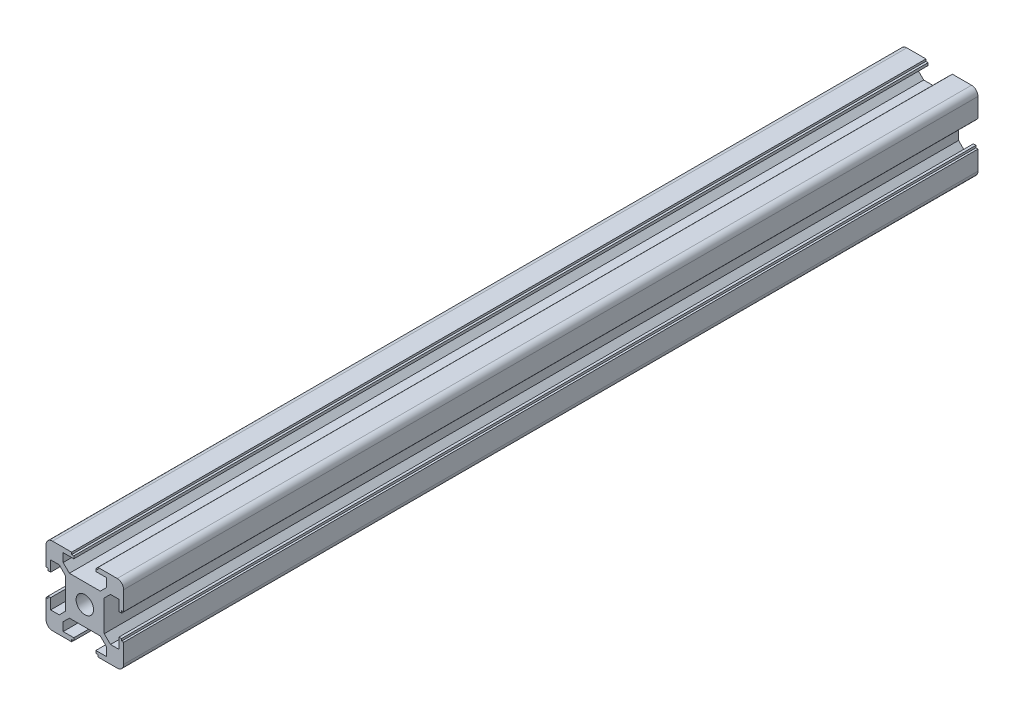
SolidWorks part; units mm, degrees
ref_plane "Front Plane" through (0, 0, 0) normal (0, 0, 1) x (1, 0, 0)
ref_plane "Top Plane" through (0, 0, 0) normal (0, 1, 0) x (1, 0, 0)
ref_plane "Right Plane" through (0, 0, 0) normal (1, 0, 0) x (0, 0, -1)
sketch "Sketch1" plane through (0, 0, 0) normal (0, 0, 1) x (1, 0, 0)
  line L1 (-15, -15) -> (15, -15)
  line L2 (-15, -15) -> (-15, 15)
  line L3 (-15, 15) -> (15, 15)
  line L4 (15, -15) -> (15, 15)
  line L5 (-15, -15) -> (15, 15) construction
  line L6 (-15, 15) -> (15, -15) construction
  point P0 (0, 0)
  dimension "D1" = 30
  dimension "D2" = 30
extrude "Boss-Extrude1" add sketch "Sketch1" along normal mid plane 330
sketch "Sketch2" plane through (0, 0, 165) normal (0, 0, 1) x (1, 0, 0)
  circle A0 centre (0, 0) radius 3.375
  dimension "D1" = 6.75
extrude "Cut-Extrude1" cut sketch "Sketch2" against normal through all
cosmetic thread "Cosmetic Thread1" parameters "D1"=12, "D2"=8
cosmetic thread "Cosmetic Thread2" parameters "D1"=12, "D2"=8
fillet "Fillet1" radius 2.5 4 edges at (15, -15, 0) (-15, -15, 0) (15, 15, 0) (-15, 15, 0)
sketch "Sketch3" plane through (0, 0, 165) normal (0, 0, 1) x (1, 0, 0)
  line L0 (0, -1000) -> (0, 49000) construction
  line L1 (0, 15) -> (-5.1, 15)
  line L2 (12.5, 15) -> (-12.5, 15) construction
  line L3 (-5.1, 15) -> (-5.1, 14.2)
  line L4 (-5.1, 14.2) -> (-4.25, 14.2)
  line L5 (-4.25, 14.2) -> (-4.25, 13.2)
  line L6 (-4.25, 13.2) -> (-8.375, 13.2)
  line L7 (-8.375, 13.2) -> (-8.375, 9.9)
  line L8 (-8.375, 9.9) -> (-5.975, 7.5)
  line L9 (-5.975, 7.5) -> (0, 7.5)
  line L10 (0, 7.5) -> (0, 15)
  dimension "D1" = 5.1
  dimension "D2" = 4.25
  dimension "D3" = 1.8
  dimension "D4" = 1
  dimension "D5" = 3.3
  dimension "D6" = 8.375
  dimension "D7" = 135
  dimension "D8" = 7.5
extrude "Cut-Extrude2" cut sketch "Sketch3" against normal through all
mirror "Mirror1" about plane through (0, 0, 0) normal (1, 0, 0) of "Cut-Extrude2"
pattern_circular "CirPattern1" count 4 over 360 about axis through (0, 0, -165) along (0, 0, 1) of "Mirror1"
